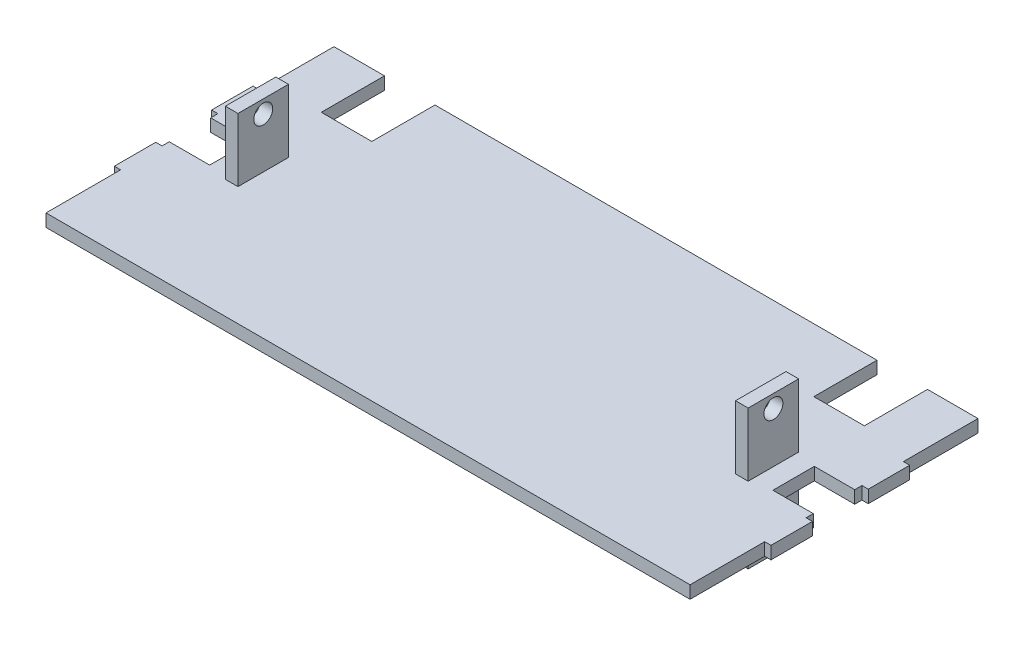
SolidWorks part; units mm, degrees
ref_plane "Front Plane" through (0, 0, 0) normal (0, 0, 1) x (1, 0, 0)
ref_plane "Top Plane" through (0, 0, 0) normal (0, 1, 0) x (1, 0, 0)
ref_plane "Right Plane" through (0, 0, 0) normal (1, 0, 0) x (0, 0, -1)
sketch "Sketch1" plane through (0, 0, 0) normal (0, 1, 0) x (1, 0, 0)
  line L0 (0, 72.39) -> (0, -72.39) construction
  line L1 (161.925, -72.39) -> (-161.925, -72.39)
  line L2 (161.925, -72.39) -> (161.925, -34.8747)
  line L3 (161.925, 72.39) -> (136.525, 72.39)
  line L4 (-161.925, -72.39) -> (-161.925, -34.8747)
  line L5 (161.925, -72.39) -> (-161.925, 72.39) construction
  line L6 (161.925, 72.39) -> (-161.925, -72.39) construction
  line L7 (161.925, 10.414) -> (141.605, 10.414)
  line L9 (161.925, -10.414) -> (141.605, -10.414)
  line L10 (141.605, 10.414) -> (141.605, -10.414)
  line L11 (-136.525, 72.39) -> (-161.925, 72.39)
  line L13 (-161.925, -10.414) -> (-141.605, -10.414)
  line L14 (-141.605, 10.414) -> (-141.605, -10.414)
  line L15 (-161.925, 10.414) -> (-141.605, 10.414)
  line L17 (-127, 0) -> (127, 0) construction
  line L18 (-161.925, 14.0467) -> (-165.1, 14.0467)
  line L20 (-161.925, 34.8747) -> (-165.1, 34.8747)
  line L21 (-165.1, 14.0467) -> (-165.1, 34.8747)
  line L22 (-161.925, -34.8747) -> (-165.1, -34.8747)
  line L23 (-165.1, -14.0467) -> (-165.1, -34.8747)
  line L24 (-161.925, -14.0467) -> (-165.1, -14.0467)
  line L27 (161.925, -14.0467) -> (165.1, -14.0467)
  line L28 (165.1, -14.0467) -> (165.1, -34.8747)
  line L29 (161.925, -34.8747) -> (165.1, -34.8747)
  line L30 (161.925, 34.8747) -> (165.1, 34.8747)
  line L31 (165.1, 14.0467) -> (165.1, 34.8747)
  line L32 (161.925, 14.0467) -> (165.1, 14.0467)
  line L34 (-161.925, 34.8747) -> (-161.925, 72.39)
  line L35 (-161.925, -14.0467) -> (-161.925, -10.414)
  line L36 (161.925, 34.8747) -> (161.925, 72.39)
  line L37 (161.925, -14.0467) -> (161.925, -10.414)
  line L38 (-161.925, 10.414) -> (-161.925, 14.0467)
  line L39 (161.925, 10.414) -> (161.925, 14.0467)
  line L40 (-136.525, 72.39) -> (-136.525, 40.64)
  line L41 (-136.525, 40.64) -> (-111.125, 40.64)
  line L42 (-111.125, 72.39) -> (-111.125, 40.64)
  line L44 (111.125, 72.39) -> (111.125, 40.64)
  line L45 (111.125, 40.64) -> (136.525, 40.64)
  line L46 (136.525, 72.39) -> (136.525, 40.64)
  line L47 (111.125, 72.39) -> (-111.125, 72.39)
  point P0 (0, 0)
  point P6 (127, 0)
  dimension "D1" = 323.85
  dimension "D2" = 144.78
  dimension "D3" = 20.828
  dimension "D5" = 3.175
  dimension "D6" = 20.828
  dimension "D4" = 20.32
  dimension "D7" = 31.75
  dimension "D8" = 25.4
  dimension "D9" = 25.4
  dimension "D10" = 31.75
  dimension "D12" = 25.4
  dimension "D11" = 25.4
extrude "Boss-Extrude1" add sketch "Sketch1" along normal mid plane 6.35
sketch "Sketch2" plane through (0, 0, 0) normal (0, 1, 0) x (1, 0, 0)
  line L0 (-141.605, 10.414) -> (-141.605, -10.414) construction
  line L1 (125.095, -12.7) -> (131.445, -12.7)
  line L2 (125.095, -12.7) -> (125.095, 12.7)
  line L3 (125.095, 12.7) -> (131.445, 12.7)
  line L4 (131.445, -12.7) -> (131.445, 12.7)
  line L5 (125.095, -12.7) -> (131.445, 12.7) construction
  line L6 (125.095, 12.7) -> (131.445, -12.7) construction
  line L9 (-125.095, -12.7) -> (-125.095, 12.7)
  line L10 (-125.095, 12.7) -> (-131.445, 12.7)
  line L11 (-131.445, -12.7) -> (-131.445, 12.7)
  line L12 (-125.095, -12.7) -> (-131.445, -12.7)
  line L13 (141.605, -10.414) -> (141.605, 10.414) construction
  point P0 (128.27, 0)
  point P10 (141.605, 0)
  dimension "D1" = 10.16
  dimension "D2" = 10.16
  dimension "D3" = 25.4
  dimension "D4" = 25.4
  dimension "D5" = 6.35
  dimension "D6" = 6.35
  dimension "D7" = 6.35
extrude "Boss-Extrude2" add sketch "Sketch2" along normal mid plane 70.104
sketch "Sketch3" plane through (-131.445, 0, 0) normal (-1, 0, 0) x (0, 0, 1)
  circle A0 centre (0, 28.4406) radius 4.7625
  circle A1 centre (0, -28.4406) radius 4.7625
  dimension "D1" = 9.525
  dimension "D2" = 9.525
extrude "Cut-Extrude1" cut sketch "Sketch3" against normal through all both and the other way through all
equation "\"length\"=12.75"
equation "\"width\"= 5.7"
equation "\"height\"= 0.25"
equation "\"D1@Sketch1\"=\"length\""
equation "\"D2@Sketch1\"=\"width\""
equation "\"eyebolt width\"= 0.82"
equation "\"eyebolt length\"= 0.8"
equation "\"D3@Sketch1\"=\"eyebolt width\""
equation "\"D4@Sketch1\"=\"eyebolt length\""
equation "\"lead screw holder height\"= 2.76"
equation "\"lead screw diameter\"=0.375"
equation "\"D1@Sketch3\"=\"lead screw diameter\""
equation "\"distance from holders to board\"=0.4"
equation "\"D2@Sketch3\"=\"lead screw diameter\""
